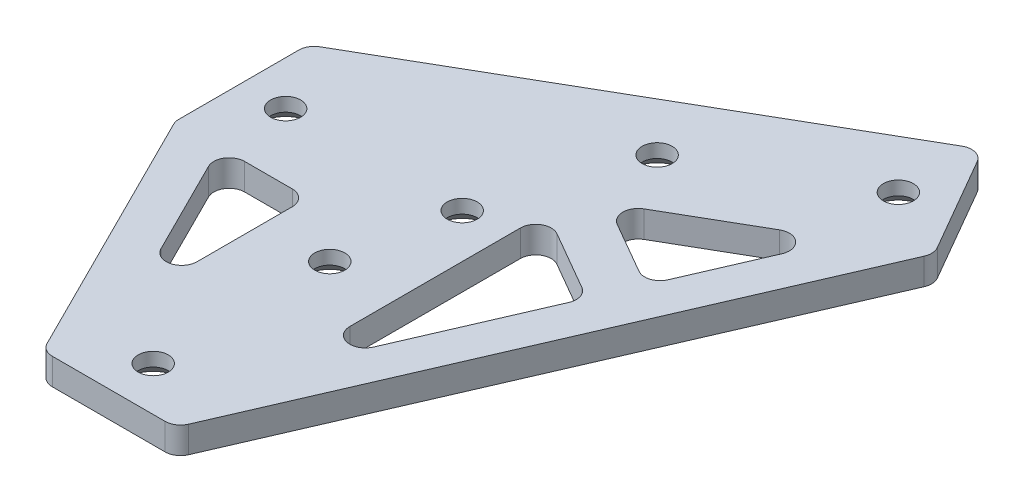
SolidWorks part; units mm, degrees
ref_plane "正面" through (0, 0, 0) normal (0, 0, 1) x (1, 0, 0)
ref_plane "平面" through (0, 0, 0) normal (0, 1, 0) x (1, 0, 0)
ref_plane "右側面" through (0, 0, 0) normal (1, 0, 0) x (0, 0, -1)
sketch "ｽｹｯﾁ2" plane through (0, 0.3953, 0) normal (0, 1, 0) x (1, 0, 0)
  line L0 (275.032, 154.7676) -> (267.532, 167.7579) construction
  line L1 (267.532, 167.7579) -> (163.6089, 107.7579) construction
  line L2 (163.6089, 107.7579) -> (171.1089, 94.7676) construction
  line L3 (171.1089, 94.7676) -> (275.032, 154.7676) construction
  line L4 (171.1089, 79.7676) -> (156.1089, 79.7676) construction
  line L5 (156.1089, 79.7676) -> (156.1089, -61.2324) construction
  line L6 (156.1089, -61.2324) -> (171.1089, -61.2324) construction
  line L7 (171.1089, -61.2324) -> (171.1089, 79.7676) construction
  line L8 (171.1089, 79.7676) -> (171.1089, 94.7676) construction
  line L9 (171.1089, 94.7676) -> (-48.8911, 94.7676) construction
  line L10 (-48.8911, 94.7676) -> (-48.8911, 79.7676) construction
  line L11 (-48.8911, 79.7676) -> (171.1089, 79.7676) construction
  line L12 (275.032, 154.7676) -> (267.532, 167.7579) construction
  line L13 (267.532, 167.7579) -> (163.6089, 107.7579) construction
  line L14 (163.6089, 107.7579) -> (171.1089, 94.7676) construction
  line L15 (171.1089, 94.7676) -> (275.032, 154.7676) construction
  line L16 (171.1089, 79.7676) -> (156.1089, 79.7676) construction
  line L17 (156.1089, 79.7676) -> (156.1089, -61.2324) construction
  line L18 (156.1089, -61.2324) -> (171.1089, -61.2324) construction
  line L19 (171.1089, -61.2324) -> (171.1089, 79.7676) construction
  line L20 (171.1089, 79.7676) -> (171.1089, 94.7676) construction
  line L21 (171.1089, 94.7676) -> (-48.8911, 94.7676) construction
  line L22 (-48.8911, 94.7676) -> (-48.8911, 79.7676) construction
  line L23 (-48.8911, 79.7676) -> (171.1089, 79.7676) construction
  line L24 (0, 15) -> (103.923, 75) construction
  line L25 (0, 0) -> (-220, 0) construction
  line L26 (0, 0) -> (0, 15) construction
  line L27 (0, 15) -> (-220, 15) construction
  line L28 (-220, 0) -> (-220, 15) construction
  line L29 (0, 0) -> (-15, 0) construction
  line L30 (0, 0) -> (0, -141) construction
  line L31 (0, -141) -> (-15, -141) construction
  line L32 (-15, 0) -> (-15, -141) construction
  line L33 (103.923, 75) -> (96.423, 87.9904) construction
  line L34 (96.423, 87.9904) -> (-7.5, 27.9904) construction
  line L35 (-7.5, 27.9904) -> (0, 15) construction
  dimension "D1" = 15
  dimension "D2" = 220
  dimension "D3" = 141
  dimension "D4" = 15
  dimension "D5" = 120
  dimension "D6" = 15
  dimension "D7" = 120
sketch "ｽｹｯﾁ4" plane through (0, 0, 0) normal (0, 1, 0) x (1, 0, 0)
  line L0 (103.923, 75) -> (96.423, 87.9904) construction
  line L1 (0, 15) -> (103.923, 75) construction
  line L2 (96.423, 87.9904) -> (-7.5, 27.9904) construction
  line L3 (-7.5, 27.9904) -> (0, 15) construction
  line L4 (0, -141) -> (-15, -141) construction
  line L5 (0, 0) -> (0, -141) construction
  line L6 (-15, 0) -> (-15, -141) construction
  line L7 (0, 0) -> (0, 15) construction
  line L8 (-220, 0) -> (-220, 15) construction
  line L9 (0, 0) -> (-220, 0) construction
  line L10 (0, 15) -> (-220, 15) construction
  line L11 (103.923, 75) -> (96.423, 87.9904) construction
  line L12 (0, 15) -> (103.923, 75) construction
  line L13 (96.423, 87.9904) -> (-7.5, 27.9904) construction
  line L14 (-7.5, 27.9904) -> (0, 15) construction
  line L15 (0, -141) -> (-15, -141) construction
  line L16 (0, 0) -> (0, -141) construction
  line L17 (-15, 0) -> (-15, -141) construction
  line L18 (0, 0) -> (0, 15) construction
  line L19 (-220, 0) -> (-220, 15) construction
  line L20 (0, 0) -> (-220, 0) construction
  line L21 (0, 15) -> (-220, 15) construction
  line L22 (-3.75, 21.4952) -> (17.9006, 33.9952) construction
  line L23 (0, 7.5) -> (-25, 7.5) construction
  line L24 (-7.5, 0) -> (-7.5, -25) construction
  line L25 (-30, 0) -> (-30, 15)
  line L26 (-30, 15) -> (18.4808, 42.9904)
  line L27 (18.4808, 42.9904) -> (25.9808, 30)
  line L28 (25.9808, 30) -> (0, -30)
  line L29 (0, -30) -> (-15, -30)
  line L30 (-15, -30) -> (-30, 0)
  circle A0 centre (0.5801, 23.9952) radius 1.6
  circle A1 centre (-5, 7.5) radius 1.6
  circle A2 centre (-7.5, -5) radius 1.6
  circle A3 centre (-7.5, -25) radius 1.6
  circle A4 centre (-25, 7.5) radius 1.6
  circle A5 centre (17.9006, 33.9952) radius 1.6
  dimension "D4" = 3.2
  dimension "D5" = 3.2
  dimension "D6" = 3.2
  dimension "D7" = 3.2
  dimension "D8" = 3.2
  dimension "D9" = 3.2
  dimension "D1" = 25
  dimension "D2" = 25
  dimension "D3" = 25
  dimension "D10" = 20
  dimension "D11" = 20
  dimension "D12" = 20
  dimension "D13" = 5
  dimension "D14" = 5
  dimension "D15" = 5
extrude "ﾎﾞｽ - 押し出し1" add sketch "ｽｹｯﾁ4" along normal mid plane 3
sketch "ｽｹｯﾁ5" plane through (0, 1.5, 0) normal (0, 1, 0) x (1, 0, 0)
  line L0 (-7.5, 27.9904) -> (0, 15) construction
  line L1 (0, 15) -> (103.923, 75) construction
  line L2 (0, 0) -> (0, 15) construction
  line L3 (0, 15) -> (-220, 15) construction
  line L4 (0, 0) -> (-220, 0) construction
  line L5 (-15, 0) -> (-15, -141) construction
  line L6 (-30, 0) -> (-15, -30)
  line L7 (-15, -30) -> (0, -30)
  line L8 (0, -30) -> (25.9808, 30)
  line L9 (25.9808, 30) -> (18.4808, 42.9904)
  line L10 (18.4808, 42.9904) -> (-30, 15)
  line L11 (-30, 15) -> (-30, 0)
  line L12 (-30, 0) -> (-15, -30)
  line L13 (-15, -30) -> (0, -30)
  line L14 (0, -30) -> (25.9808, 30)
  line L15 (25.9808, 30) -> (18.4808, 42.9904)
  line L16 (18.4808, 42.9904) -> (-30, 15)
  line L17 (-30, 15) -> (-30, 0)
  line L18 (0, 0) -> (0, -141) construction
  line L19 (-7.5, 27.9904) -> (0, 15)
  line L20 (0, 15) -> (103.923, 75)
  line L21 (0, 0) -> (0, 15)
  line L22 (0, 15) -> (-220, 15)
  line L23 (0, 0) -> (-220, 0)
  line L24 (-15, 0) -> (-15, -141)
  line L25 (0, 0) -> (0, -141)
  line L26 (-2.9552, -25.5) -> (20.9517, 29.7106)
  line L27 (20.9517, 29.7106) -> (16.8336, 36.8433)
  line L28 (16.8336, 36.8433) -> (-25.5, 12.4019)
  line L29 (-25.5, 12.4019) -> (-25.5, 1.0623)
  line L30 (-25.5, 1.0623) -> (-12.2188, -25.5)
  line L31 (-12.2188, -25.5) -> (-2.9552, -25.5)
  line L32 (0, 15) -> (11.6654, 8.265) construction
  line L33 (0, 15) -> (-10.5, 21.0622) construction
  line L34 (-13, 19.6188) -> (10.6654, 5.9555)
  line L37 (-21, 15) -> (-5.25, 24.0933) construction
  line L38 (12.6654, 10.5744) -> (-8, 22.5056)
  line L40 (0, 15) -> (3.4641, 13)
  line L41 (0, 15) -> (-3.4641, 17)
  line L42 (-4.6188, 15) -> (-2.3094, 19)
  line L43 (0, 7) -> (6.9282, 19)
  line L44 (1.25, 17.1651) -> (-9.25, 23.2272) construction
  line L47 (-1.25, 12.8349) -> (10.4154, 6.0999) construction
  circle A1 centre (0.5801, 23.9952) radius 1.6
  circle A2 centre (0.5801, 23.9952) radius 1.6
  circle A3 centre (-5, 7.5) radius 1.6
  circle A4 centre (-5, 7.5) radius 1.6
  circle A5 centre (-7.5, -5) radius 1.6
  circle A6 centre (-7.5, -5) radius 1.6
  circle A7 centre (-7.5, -25) radius 1.6
  circle A8 centre (-7.5, -25) radius 1.6
  circle A9 centre (-25, 7.5) radius 1.6
  circle A10 centre (-25, 7.5) radius 1.6
  circle A11 centre (17.9006, 33.9952) radius 1.6
  circle A12 centre (17.9006, 33.9952) radius 1.6
  point P58 (-3.4641, 17)
  point P61 (3.4641, 13)
  dimension "D9" = 2.5
  dimension "D12" = 60
  dimension "D13" = 4
  dimension "D14" = 4
  dimension "D1" = 0
  dimension "D2" = 0
  dimension "D3" = 0
  dimension "D4" = 0
  dimension "D5" = 0
  dimension "D6" = 0
  dimension "D7" = 0
  dimension "D8" = 4.5
extrude "ｶｯﾄ - 押し出し2" cut sketch "ｽｹｯﾁ5" against normal blind 3 contours L43 L38 L26 L20 | L38 L43 L20 | L21 L43 L34 | L43 L21 L25 L26 L34 | L23 L30 L24 region at (-18.3229, 1.5, 6.6459) region at (3.6557, 1.5, 0.5658) region at (11.9477, 1.5, -17.8006) region at (0.738, 1.5, -9.9827) region at (4.7141, 1.5, -16.8695)
fillet "ﾌｨﾚｯﾄ2" radius 1.75 15 edges at (-15, 0, 19.9377) (0, 0, 18.6752) (10.6654, 0, -5.9555) (12.6654, 0, -10.5744) (2.5, 0, -16.4434) (19.4424, 0, -26.2251) (-24.9688, 0, 0) (-15, 0, 30) (0, 0, 30) (25.9808, 0, -30) (18.4808, 0, -42.9904) (-30, 0, -15) (-30, 0, 0) (0, 0, -12.1132) (-15, 0, 0)
sketch "ｽｹｯﾁ6" plane through (0, -1.5, 0) normal (0, -1, 0) x (1, 0, 0)
  line L3 (2.625, -10.5977) -> (9.3148, -6.7353)
  line L4 (0, 10.2297) -> (0, -9.0822)
  line L5 (10.0457, -4.5244) -> (3.3559, 10.9251)
  line L6 (2.625, -10.5977) -> (9.3148, -6.7353)
  line L7 (0, 10.2297) -> (0, -9.0822)
  line L8 (10.0457, -4.5244) -> (3.3559, 10.9251)
  line L9 (-15, 1.75) -> (-15, 12.5246)
  line L10 (-22.1373, 0) -> (-16.75, 0)
  line L11 (-18.3152, 13.3072) -> (-23.7025, 2.5326)
  line L12 (-15, 1.75) -> (-15, 12.5246)
  line L13 (-22.1373, 0) -> (-16.75, 0)
  line L14 (-18.3152, 13.3072) -> (-23.7025, 2.5326)
  line L15 (10.9648, -11.5562) -> (5.125, -14.9278)
  line L16 (17.339, -21.3674) -> (13.4457, -12.3764)
  line L17 (5.125, -17.9589) -> (14.8581, -23.5783)
  line L18 (10.9648, -11.5562) -> (5.125, -14.9278)
  line L19 (17.339, -21.3674) -> (13.4457, -12.3764)
  line L20 (5.125, -17.9589) -> (14.8581, -23.5783)
  circle A1 centre (-25, -7.5) radius 1.6
  circle A2 centre (-25, -7.5) radius 1.6
  arc A3 (0, -9.0822) -> (2.625, -10.5977) centre (1.75, -9.0822) ccw
  arc A4 (3.3559, 10.9251) -> (0, 10.2297) centre (1.75, 10.2297) ccw
  arc A5 (9.3148, -6.7353) -> (10.0457, -4.5244) centre (8.4398, -5.2198) ccw
  arc A6 (0, -9.0822) -> (2.625, -10.5977) centre (1.75, -9.0822) ccw
  arc A7 (3.3559, 10.9251) -> (0, 10.2297) centre (1.75, 10.2297) ccw
  arc A8 (9.3148, -6.7353) -> (10.0457, -4.5244) centre (8.4398, -5.2198) ccw
  arc A9 (-16.75, 0) -> (-15, 1.75) centre (-16.75, 1.75) ccw
  arc A10 (-23.7025, 2.5326) -> (-22.1373, 0) centre (-22.1373, 1.75) ccw
  arc A11 (-15, 12.5246) -> (-18.3152, 13.3072) centre (-16.75, 12.5246) ccw
  arc A12 (-16.75, 0) -> (-15, 1.75) centre (-16.75, 1.75) ccw
  arc A13 (-23.7025, 2.5326) -> (-22.1373, 0) centre (-22.1373, 1.75) ccw
  arc A14 (-15, 12.5246) -> (-18.3152, 13.3072) centre (-16.75, 12.5246) ccw
  circle A15 centre (-7.5, 5) radius 1.6
  circle A16 centre (-7.5, 5) radius 1.6
  circle A17 centre (0.5801, -23.9952) radius 1.6
  circle A18 centre (0.5801, -23.9952) radius 1.6
  circle A19 centre (-5, -7.5) radius 1.6
  circle A20 centre (-5, -7.5) radius 1.6
  circle A21 centre (-7.5, 25) radius 1.6
  circle A22 centre (-7.5, 25) radius 1.6
  circle A23 centre (17.9006, -33.9952) radius 1.6
  circle A24 centre (17.9006, -33.9952) radius 1.6
  arc A27 (13.4457, -12.3764) -> (10.9648, -11.5562) centre (11.8398, -13.0717) ccw
  arc A28 (14.8581, -23.5783) -> (17.339, -21.3674) centre (15.7331, -22.0628) ccw
  arc A29 (5.125, -14.9278) -> (5.125, -17.9589) centre (6, -16.4434) ccw
  arc A30 (13.4457, -12.3764) -> (10.9648, -11.5562) centre (11.8398, -13.0717) ccw
  arc A31 (14.8581, -23.5783) -> (17.339, -21.3674) centre (15.7331, -22.0628) ccw
  arc A32 (5.125, -14.9278) -> (5.125, -17.9589) centre (6, -16.4434) ccw
  dimension "D1" = 0
  dimension "D2" = 0
  dimension "D3" = 0
  dimension "D4" = 0
  dimension "D5" = 0
  dimension "D6" = 0
  dimension "D7" = 0
  dimension "D8" = 0
  dimension "D9" = 0
hole_wizard "M3 丸皿ねじ用皿穴1" positions "3Dｽｹｯﾁ1" profile "ｽｹｯﾁ7" countersink size "M3" standard "ISO"
sketch3d "3Dｽｹｯﾁ1"
  point P0 (-7.5, -1.5, 25)
  point P3 (-7.5, -1.5, 5)
  point P6 (-25, -1.5, -7.5)
  point P9 (-5, -1.5, -7.5)
  point P12 (0.5801, -1.5, -23.9952)
  point P15 (17.9006, -1.5, -33.9952)
sketch "ｽｹｯﾁ7" plane through (-7.5, -1.5, 25) normal (1, 0, 0) x (0, 0, -1)
  line L0 (0, 0) -> (0, 7)
  line L1 (0, 7) -> (1.7, 5.9785)
  line L2 (1.7, 5.9785) -> (1.7, 1.45)
  line L3 (1.7, 1.45) -> (3.15, 0)
  line L5 (3.15, 0) -> (0, 0)
  line L6 (-1.7, 1.45) -> (-3.15, 0) construction
  line L10 (0, 7) -> (-1.7, 5.9785) construction
  line L11 (0, -6.35) -> (0, 107.95) construction
  dimension "穴の直径" = 3.4
  dimension "穴の深さ" = 7
  dimension "表面の皿穴の直径" = 6.3
  dimension "表面の皿穴の角度" = 90
  dimension "ﾄﾞﾘﾙ角度" = 118
